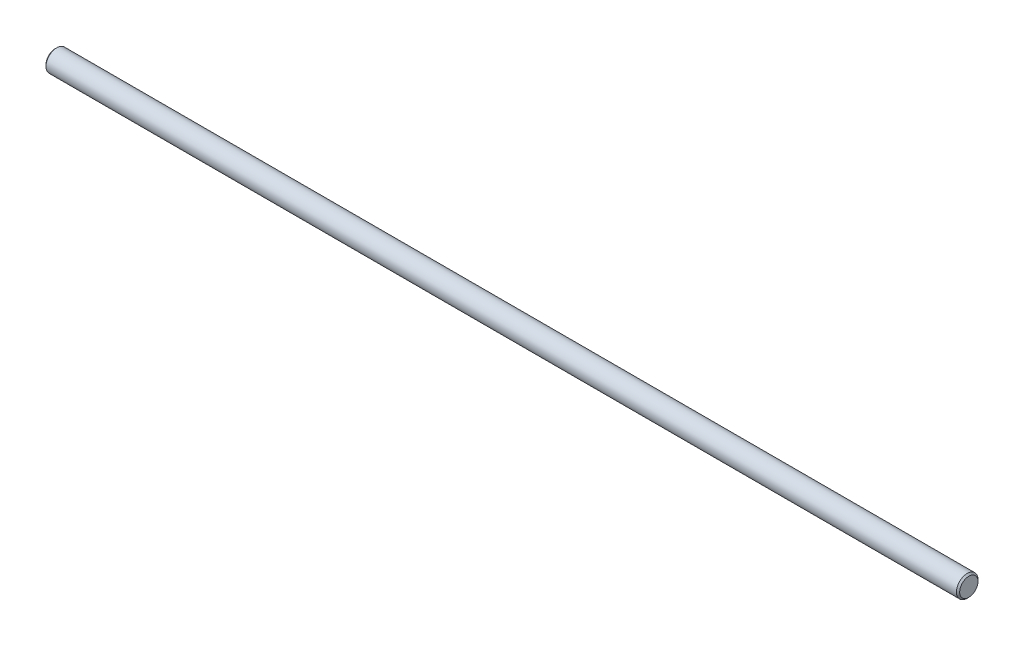
SolidWorks part; units mm, degrees
ref_plane "Front Plane" through (0, 0, 0) normal (0, 0, 1) x (1, 0, 0)
ref_plane "Top Plane" through (0, 0, 0) normal (0, 1, 0) x (1, 0, 0)
ref_plane "Right Plane" through (0, 0, 0) normal (1, 0, 0) x (0, 0, -1)
sketch "Sketch1" plane through (0, 0, 0) normal (0, 0, 1) x (1, 0, 0)
  line L0 (-168.275, 0) -> (168.275, 0) construction
  line L1 (168.275, 3.9688) -> (168.275, -3.9688) construction
  line L2 (-168.275, 3.9688) -> (-168.275, -3.9688) construction
  point P6 (165.4969, -3.9688)
  dimension "Thread Diameter" = 7.9375
  dimension "Length" = 336.55
  dimension "D1" = 2.7781
sketch "Sketch2" plane through (0, 0, 0) normal (1, 0, 0) x (0, 0, -1)
  circle A0 centre (0, 0) radius 3.9688
extrude "Boss-Extrude1" add sketch "Sketch2" against normal up to vertex (168.275 mm away) and the other way up to vertex (168.275 mm away) up to point (-168.275, 0, 0) other way up to point (168.275, 0, 0)
cosmetic thread "Cosmetic Thread1" parameters "D2"=3.8811
sketch "Sketch3" plane through (168.275, 0, 0) normal (1, 0, 0) x (0, 0, -1)
  circle A1 centre (0, 0) radius 3.9688
  circle A2 centre (0, 0) radius 3.9688
  dimension "D1" = 0
curve "Helix/Spiral1" pitch 0.7937 height 337.3438 turns 425 parameters "Pitch"=0.7937
chamfer "Chamfer1" distance 0.5953 angle 45 2 edges at (-168.275, 0, -3.9688) (168.275, 0, -3.9688)
sketch "Sketch4" plane through (0, 0, 0) normal (0, 0, 1) x (1, 0, 0)
  line L0 (168.2254, 4.0547) -> (168.6223, 3.3673) construction
  line L1 (168.6223, 3.3673) -> (169.0191, 4.0547) construction
  line L2 (169.0191, 4.0547) -> (168.2254, 4.0547) construction
  line L3 (168.6223, 4.0547) -> (168.6223, 3.9688) construction
  line L4 (168.6223, 3.3673) -> (168.6223, 3.4532) construction
  line L5 (168.5727, 3.4532) -> (168.6719, 3.4532) construction
  line L6 (168.275, 3.9688) -> (168.9695, 3.9688) construction
  line L7 (168.5727, 3.4532) -> (168.2502, 4.0117)
  line L8 (168.5727, 3.4532) -> (168.6719, 3.4532)
  line L9 (168.2502, 4.0117) -> (168.9943, 4.0117)
  line L10 (168.9943, 4.0117) -> (168.6719, 3.4532)
  point P13 (168.6223, 4.0117)
  dimension "D2" = 0.0992
sweep "Cut-Sweep3" [suppressed] cut profiles "Sketch4" path "Helix/Spiral1"
equation "\"D3@Helix/Spiral1\" = \"Length@Sketch1\"+\"Pitch@Helix/Spiral1\""
equation "\"D1@Chamfer1\" = \"Pitch@Helix/Spiral1\"*.75"
equation "\"D1@Sketch4\" = \"Pitch@Helix/Spiral1\""
equation "\"D2@Sketch4\" = \"D1@Sketch4\"/8"
equation "\"D1@Sketch1\" = \"Pitch@Helix/Spiral1\"*3.50"
